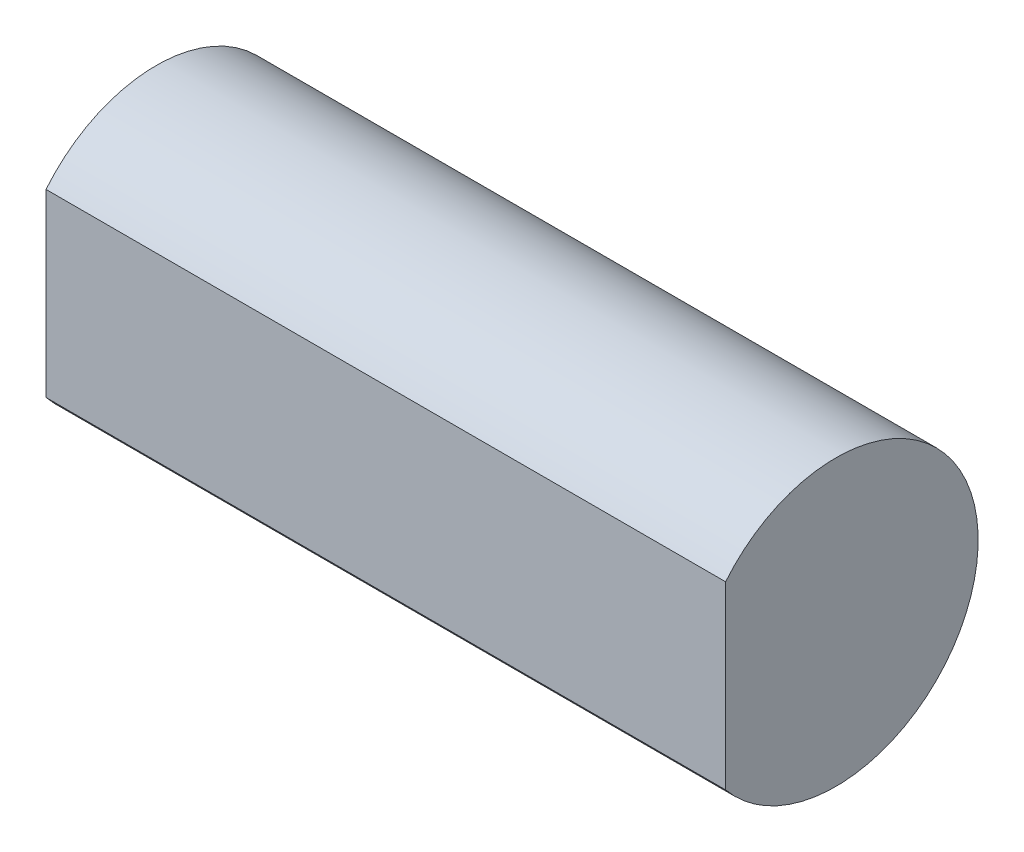
SolidWorks part; units mm, degrees
ref_plane "Alzado" through (0, 0, 0) normal (1, 0, 0) x (0, 1, 0)
ref_plane "Planta" through (0, 0, 0) normal (0, 0, 1) x (0, 1, 0)
ref_plane "Vista lateral" through (0, 0, 0) normal (0, 1, 0) x (-1, 0, 0)
sketch "Croquis1" plane through (0, 0, 0) normal (1, 0, 0) x (0, 1, 0)
  line L0 (2.4527, 3) -> (-2.4527, 3)
  arc A0 (-2.4527, 3) -> (2.4527, 3) centre (0, 0) ccw
  dimension "D1" = 7.75
  dimension "D2" = 3
extrude "Saliente-Extruir1" add sketch "Croquis1" along normal blind 18.5 contours L0 A0 region at (0, 0, -0.2223)
